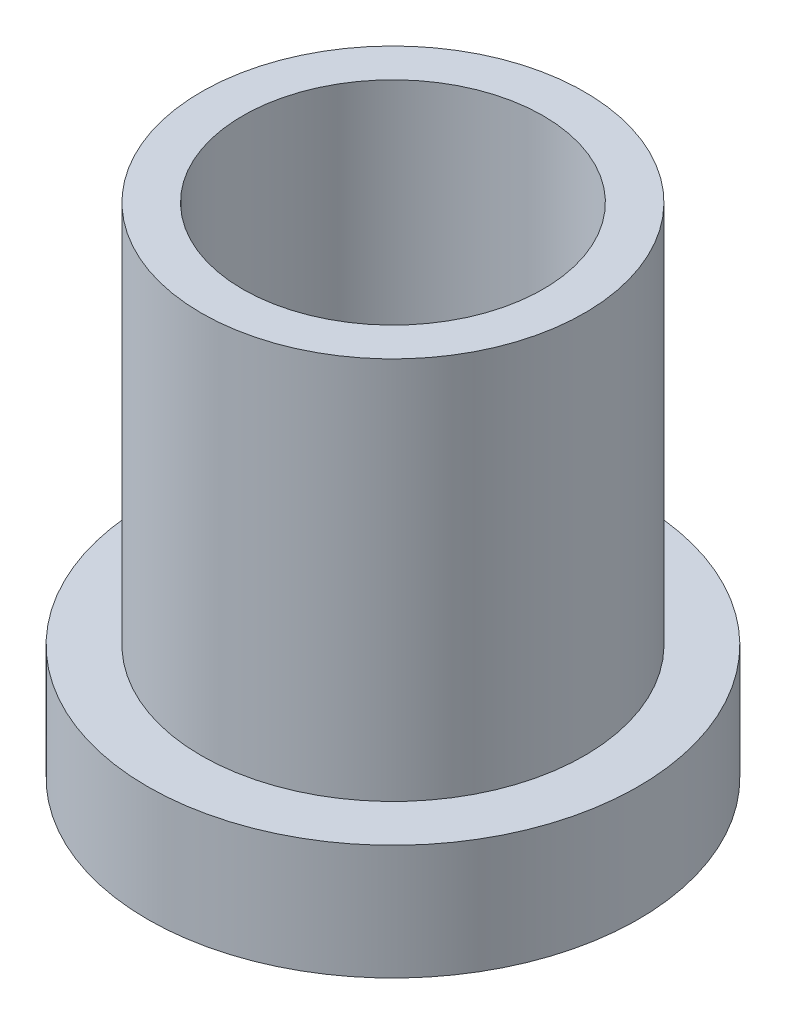
SolidWorks part; units mm, degrees
material "PET"
ref_plane "Front Plane" through (0, 0, 0) normal (0, 0, 1) x (1, 0, 0)
ref_plane "Top Plane" through (0, 0, 0) normal (0, 1, 0) x (1, 0, 0)
ref_plane "Right Plane" through (0, 0, 0) normal (1, 0, 0) x (0, 0, -1)
sketch "Sketch1" plane through (0, 0, 0) normal (0, 1, 0) x (1, 0, 0)
  circle A0 centre (0, 0) radius 3.175
  circle A1 centre (0, 0) radius 2.4892
  dimension "D1" = 6.35
  dimension "D2" = 4.9784
extrude "Boss-Extrude1" add sketch "Sketch1" along normal blind 6.35
sketch "Sketch2" plane through (0, 0, 0) normal (0, -1, 0) x (1, 0, 0)
  circle A0 centre (0, 0) radius 4.064
extrude "Boss-Extrude2" add sketch "Sketch2" along normal blind 1.905
sketch "Sketch3" plane through (0, -1.905, 0) normal (0, -1, 0) x (1, 0, 0)
  circle A0 centre (0, 0) radius 2.4892
  dimension "D1" = 4.9784
extrude "Cut-Extrude1" cut sketch "Sketch3" against normal through all
